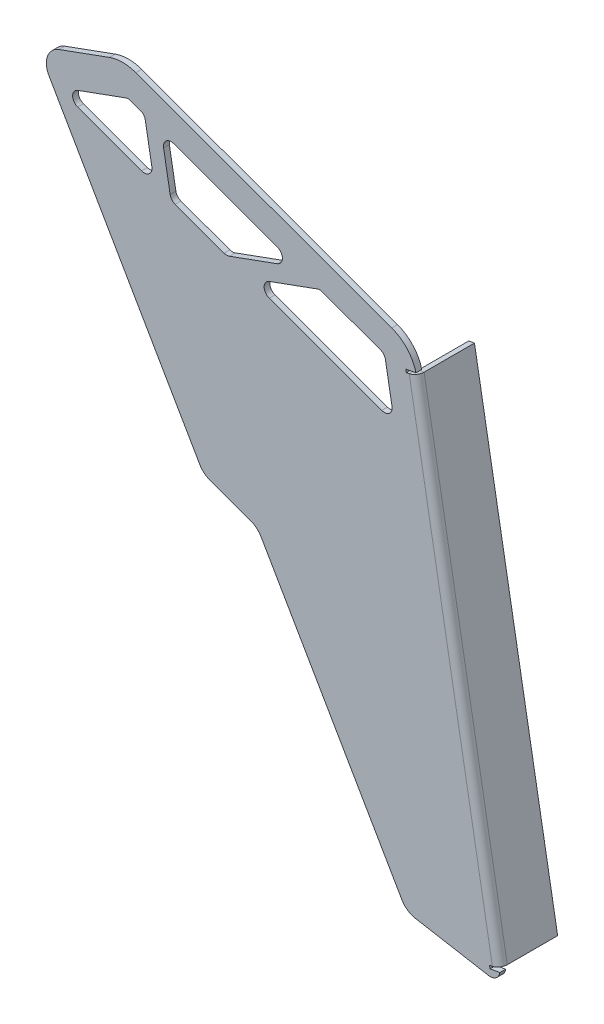
SolidWorks part; units mm, degrees
note: The reader was unsure of these and kept them because the rebuilt part matched: flange length of "Aresta-Flange1".
material "Liga 1060"
ref_plane "Plano frontal" through (0, 0, 0) normal (0, 0, 1) x (1, 0, 0)
ref_plane "Plano superior" through (0, 0, 0) normal (0, 1, 0) x (1, 0, 0)
ref_plane "Plano direito" through (0, 0, 0) normal (1, 0, 0) x (0, 0, -1)
sketch "Esboço29" plane through (0, 0, 0) normal (0, 0, 1) x (1, 0, 0)
  line L0 (181.5691, 337.9021) -> (258.5806, 204.5144) construction
  line L2 (391.7176, 57.9949) -> (417.8533, 53.3864) construction
  line L3 (295.7993, 178.5193) -> (366.6569, 55.7905) construction
  line L4 (271.6807, 193.522) -> (282.6992, 189.5116) construction
  line L5 (221.3457, 367.2366) -> (176.5504, 350.9324) construction
  line L16 (243.325, 329.0983) -> (239.9163, 348.43)
  line L17 (249.3989, 340.7219) -> (252.8076, 321.3902)
  line L18 (328.9999, 317.1387) -> (304.1476, 308.0931)
  line L19 (367.7928, 283.7957) -> (364.3841, 303.1274)
  line L20 (361.8129, 306.1916) -> (331.7361, 317.1387)
  line L21 (304.1476, 300.5756) -> (362.4854, 279.3424)
  line L22 (283.4933, 309.089) -> (308.3456, 318.1345)
  line L23 (308.3456, 325.6521) -> (254.7062, 345.1752)
  line L24 (255.3787, 318.326) -> (280.7571, 309.089)
  line L25 (237.3452, 351.4941) -> (232.478, 353.2657)
  line L26 (204.8895, 336.7026) -> (238.0177, 324.6449)
  line L27 (229.7418, 353.2657) -> (204.8895, 344.2201)
  line L28 (423.6456, 59.1787) -> (380.542, 303.6315)
  line L29 (379.8475, 60.0879) -> (417.8533, 53.3864)
  line L30 (367.6863, 318.9523) -> (235.0265, 367.2366)
  line L31 (221.3457, 367.2366) -> (195.2216, 357.7282)
  line L32 (189.9816, 343.3313) -> (268.1507, 207.9383)
  line L34 (273.3908, 203.5414) -> (294.6699, 195.7964)
  line L35 (299.91, 191.3995) -> (372.9237, 64.936)
  arc A15 (362.4854, 279.3424) -> (367.7928, 283.7957) centre (363.8535, 283.1011) ccw
  arc A16 (364.3841, 303.1274) -> (361.8129, 306.1916) centre (360.4448, 302.4328) ccw
  arc A17 (331.7361, 317.1387) -> (328.9999, 317.1387) centre (330.368, 313.3799) ccw
  arc A18 (304.1476, 308.0931) -> (304.1476, 300.5756) centre (305.5156, 304.3344) ccw
  arc A19 (308.3456, 318.1345) -> (308.3456, 325.6521) centre (306.9775, 321.8933) ccw
  arc A20 (254.7062, 345.1752) -> (249.3989, 340.7219) centre (253.3381, 341.4165) ccw
  arc A21 (252.8076, 321.3902) -> (255.3787, 318.326) centre (256.7468, 322.0848) ccw
  arc A22 (280.7571, 309.089) -> (283.4933, 309.089) centre (282.1252, 312.8478) ccw
  arc A23 (232.478, 353.2657) -> (229.7418, 353.2657) centre (231.1099, 349.5069) ccw
  arc A24 (239.9163, 348.43) -> (237.3452, 351.4941) centre (235.9771, 347.7354) ccw
  arc A25 (238.0177, 324.6449) -> (243.325, 329.0983) centre (239.3858, 328.4037) ccw
  arc A26 (204.8895, 344.2201) -> (204.8895, 336.7026) centre (206.2575, 340.4614) ccw
  arc A27 (417.8533, 53.3864) -> (423.6456, 59.1787) centre (418.7216, 58.3105) ccw
  arc A28 (380.542, 303.6315) -> (367.6863, 318.9523) centre (360.8459, 300.1585) ccw
  arc A29 (235.0265, 367.2366) -> (221.3457, 367.2366) centre (228.1861, 348.4427) ccw
  arc A30 (379.8475, 60.0879) -> (372.9237, 64.936) centre (381.584, 69.936) cw
  arc A31 (294.6699, 195.7964) -> (299.91, 191.3995) centre (291.2497, 186.3995) cw
  arc A32 (268.1507, 207.9383) -> (273.3908, 203.5414) centre (276.811, 212.9383) ccw
  arc A33 (195.2216, 357.7282) -> (189.9816, 343.3313) centre (198.6418, 348.3313) ccw
  point P57 (378.461, 60.3324)
  point P62 (269.9706, 204.7862)
  dimension "D3" = 10
  dimension "D1" = 10
  dimension "D2" = 10
  dimension "D4" = 10
extrude "Ressalto-extrusão1" add sketch "Esboço29" along normal blind 3
sheet metal parameters "Chapa metálica1" thickness 3 parameters "D1"=0.9
convert to sheet metal "Converter-Sólido1" parameters "D1"=0.9
edge flange "Aresta-Flange1" sketch "Esboço32" flange angle 90 flange length 30 bend radius 0.9 thickness 3 relief rectangular parameters "D6"=10
sketch "Esboço32" plane through (420.9913, 74.2321, 0) normal (0.9848, 0.1736, 0) x (0.1736, -0.9848, 0)
  line L0 (15.2856, 0) -> (-232.9382, 0) construction
  line L1 (15.2856, 0) -> (-232.9382, 0)
  line L2 (-232.9382, 0) -> (-232.9382, 27)
  line L3 (-232.9382, 27) -> (15.2856, 27)
  line L4 (15.2856, 27) -> (15.2856, 0)
bend "DobradeAresta1" bend radius 0.9 bend angle 90 parameters "D5"=1
flat pattern "Padrão-Plano1" [suppressed]
sketch "Curva-Linhas1" plane through (0, 0, 0) normal (0, 1, 0) x (-1, 0, 0)
sketch "Caixa delimitadora1" [suppressed] plane through (0, 0, 0) normal (0, 1, 0) x (-1, 0, 0)
bend of the flat pattern "Planificar-<DobradeAresta1>1"
